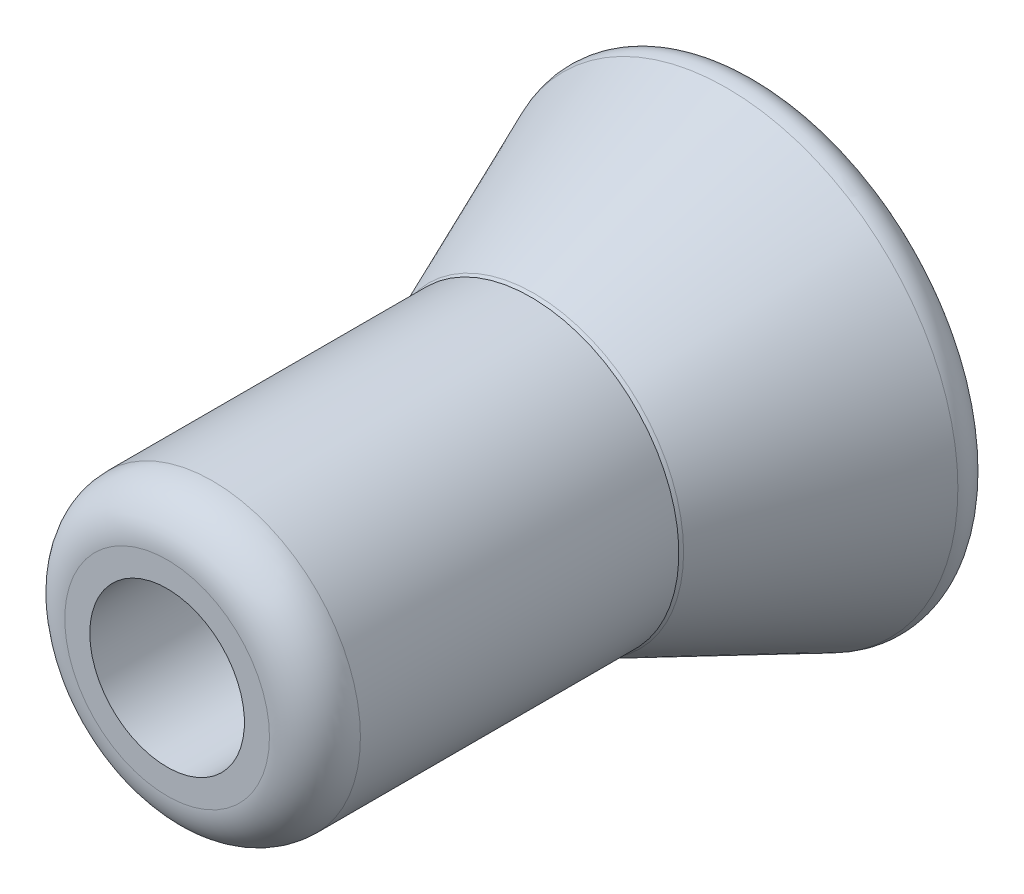
SolidWorks part; units mm, degrees
ref_plane "前视基准面" through (0, 0, 0) normal (0, 0, 1) x (1, 0, 0)
ref_plane "上视基准面" through (0, 0, 0) normal (0, 1, 0) x (1, 0, 0)
ref_plane "右视基准面" through (0, 0, 0) normal (1, 0, 0) x (0, 0, -1)
sketch "草图1" plane through (0, 0, 0) normal (0, 0, 1) x (1, 0, 0)
  circle A1 centre (0, 0) radius 3.25
  dimension "D2" = 6.5
extrude "凸台-拉伸1" add sketch "草图1" along normal blind 13
sketch "草图2" plane through (0, 0, 0) normal (0, 0, -1) x (-1, 0, 0)
  circle A0 centre (0, 0) radius 5.3758
  dimension "D1" = 10.7515
extrude "凸台-拉伸2" add sketch "草图2" against normal blind 5 draft 23
sketch "草图3" plane through (0, 0, 0) normal (0, 0, -1) x (-1, 0, 0)
  circle A0 centre (0, 0) radius 1.7
  dimension "D1" = 3.4
extrude "切除-拉伸1" cut sketch "草图3" against normal through all
fillet "圆角1" radius 1 1 edges at (3.25, 0, 13)
fillet "圆角2" radius 0.5 1 edges at (-5.3758, 0, 0)
fillet "圆角3" radius 1 1 edges at (-3.2534, 0, 5)
